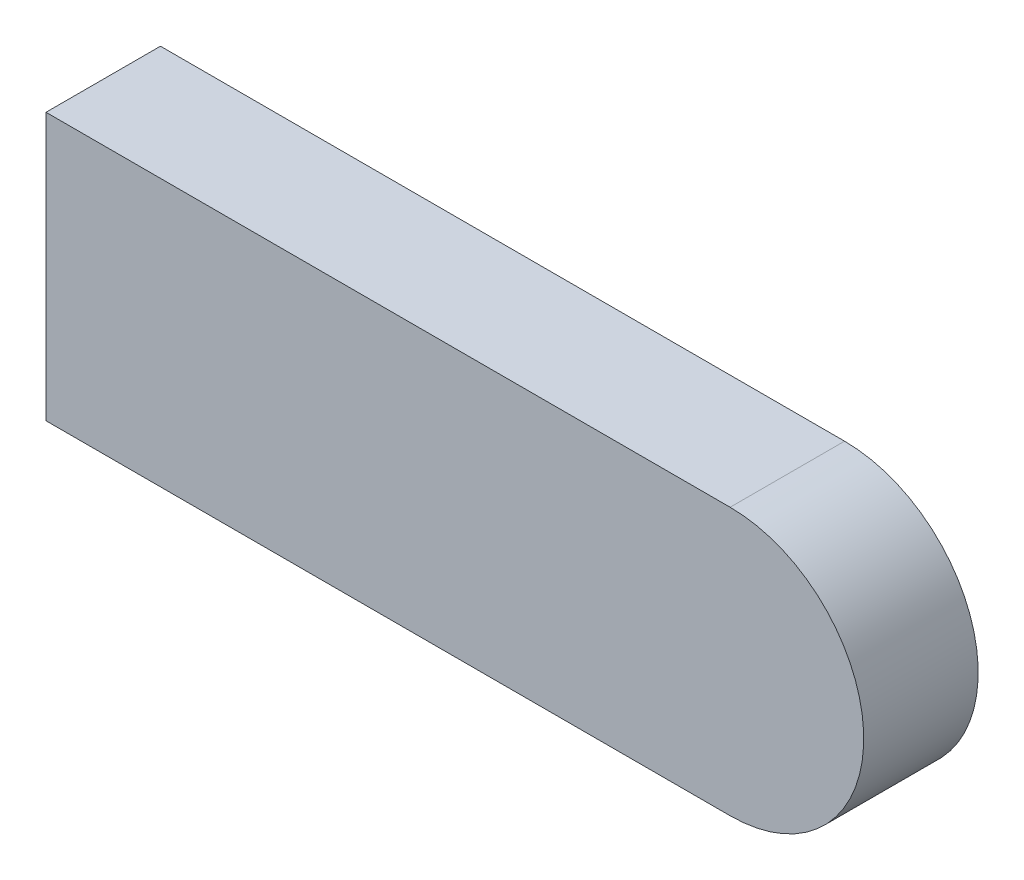
SolidWorks part; units mm, degrees
ref_plane "Front Plane" through (0, 0, 0) normal (0, 0, 1) x (1, 0, 0)
ref_plane "Top Plane" through (0, 0, 0) normal (0, 1, 0) x (1, 0, 0)
ref_plane "Right Plane" through (0, 0, 0) normal (1, 0, 0) x (0, 0, -1)
sketch "Sketch1" plane through (0, 0, 0) normal (0, 0, 1) x (1, 0, 0)
  line L0 (-1167.1066, -285.4695) -> (-1667.4041, 696.4197) construction
  line L1 (1268.0615, 2050.2455) -> (1268.0615, 1980.2088)
  line L2 (1268.0615, 1980.2088) -> (1447.3885, 1980.2088)
  line L4 (1447.3885, 2050.2455) -> (1268.0615, 2050.2455)
  arc A0 (1447.3885, 1980.2088) -> (1447.3885, 2050.2455) centre (1447.3885, 2015.2271) ccw
extrude "Boss-Extrude2" add sketch "Sketch1" along normal blind 30 contours L0 L1 L2 A0 region at (1371.6244, 2015.2271, 0)
